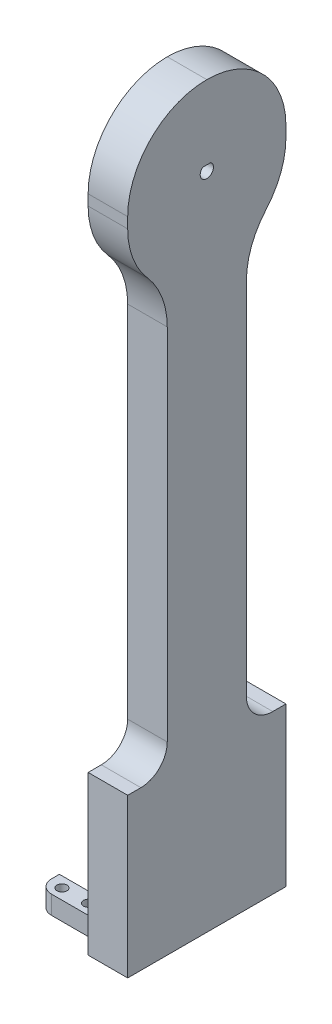
SolidWorks part; units mm, degrees
ref_plane "Front Plane" through (0, 0, 0) normal (0, 0, 1) x (1, 0, 0)
ref_plane "Top Plane" through (0, 0, 0) normal (0, 1, 0) x (1, 0, 0)
ref_plane "Right Plane" through (0, 0, 0) normal (1, 0, 0) x (0, 0, -1)
sketch "Sketch1" plane through (0, 0, 0) normal (1, 0, 0) x (0, 0, -1)
  line L1 (30, -30) -> (-30, -30)
  line L2 (30, -30) -> (30, 30)
  line L3 (30, 30) -> (-30, 30)
  line L4 (-30, -30) -> (-30, 30)
  line L5 (30, -30) -> (-30, 30) construction
  line L6 (30, 30) -> (-30, -30) construction
  point P0 (0, 0)
  dimension "D1" = 60
  dimension "D2" = 60
extrude "Boss-Extrude1" add sketch "Sketch1" along normal blind 15
sketch "Sketch2" plane through (15, 0, 0) normal (1, 0, 0) x (0, 0, -1)
  line L0 (0, 0) -> (0, 30) construction
  line L1 (30, 30) -> (-30, 30) construction
  line L2 (1.5, 2) -> (-1.5, 2)
  circle A0 centre (0, 0) radius 2.5
  dimension "D1" = 5
  dimension "D2" = 3
extrude "Cut-Extrude1" cut sketch "Sketch2" against normal up to surface (15 mm away) contours A0 region at (15, -0.1209, 0) up to face at (0, 0, 0)
sketch "Sketch8" plane through (0, -30, 0) normal (0, -1, 0) x (1, 0, 0)
  line L0 (0, 30) -> (0, 15) construction
  line L1 (0, 30) -> (0, -30) construction
  line L2 (15, 30) -> (15, -30) construction
  line L3 (0, 15) -> (15, 15)
  line L4 (0, 15) -> (0, -15)
  line L5 (0, -15) -> (15, -15)
  line L6 (15, 15) -> (15, -15)
  line L7 (0, -15) -> (0, -30) construction
  dimension "D1" = 30
extrude "Boss-Extrude2" add sketch "Sketch8" along normal blind 160
sketch "Sketch9" plane through (0, -190, 0) normal (0, -1, 0) x (1, 0, 0)
  line L0 (0, 0) -> (0, 30)
  line L1 (0, 15) -> (0, -15) construction
  line L2 (15, 30) -> (15, -30)
  line L3 (15, -30) -> (0, -30)
  line L4 (15, 30) -> (0, 30)
  line L5 (0, -30) -> (0, 0)
  dimension "D1" = 60
extrude "Boss-Extrude3" add sketch "Sketch9" along normal blind 60
sketch "Sketch10" plane through (0, 0, 0) normal (-1, 0, 0) x (0, 0, 1)
  line L0 (30, -250) -> (30, -245) construction
  line L1 (30, -250) -> (30, -190) construction
  line L2 (30, -245) -> (28.89, -245) construction
  line L3 (0, -250) -> (0, -194.4433) construction
  line L4 (28.89, -245) -> (20.89, -245)
  line L5 (28.89, -245) -> (28.89, -238)
  line L6 (28.89, -238) -> (20.89, -238)
  line L7 (20.89, -245) -> (20.89, -238)
  line L8 (30, -250) -> (-30, -250) construction
  line L9 (-20.89, -245) -> (-20.89, -238)
  line L10 (-28.89, -238) -> (-20.89, -238)
  line L11 (-28.89, -245) -> (-28.89, -238)
  line L12 (-28.89, -245) -> (-20.89, -245)
  line L13 (24.89, -245) -> (-24.89, -245) construction
  dimension "D1" = 5
  dimension "D2" = 7
  dimension "D3" = 8
  dimension "D4" = 49.78
extrude "Boss-Extrude4" add sketch "Sketch10" along normal blind 20
sketch "Sketch12" plane through (0, -245, 0) normal (0, -1, 0) x (1, 0, 0)
  line L0 (-20, 28.89) -> (-20, 24.89) construction
  line L1 (-20, 20.89) -> (-20, 28.89) construction
  line L2 (-20, 24.89) -> (-15.025, 24.89) construction
  line L3 (-15.025, 24.89) -> (-4.975, 24.89) construction
  line L4 (-4.975, 24.89) -> (0, 24.89) construction
  line L5 (0, 20.89) -> (0, 28.89) construction
  line L6 (0, 24.89) -> (0, -24.89) construction
  line L7 (0, -28.89) -> (0, -20.89) construction
  line L8 (0, 0) -> (-23.535, 0) construction
  circle A0 centre (-15.025, 24.89) radius 1.9
  circle A1 centre (-4.975, 24.89) radius 1.9
  circle A2 centre (-4.975, -24.89) radius 1.9
  circle A3 centre (-15.025, -24.89) radius 1.9
  dimension "D2" = 3.8
  dimension "D1" = 10.05
extrude "Cut-Extrude2" cut sketch "Sketch12" against normal up to surface (7 mm away) up to face at (-10, -238, 24.89)
fillet "Fillet1" radius 30 4 edges at (7.5, -30, -30) (7.5, 30, -30) (7.5, -30, 30) (7.5, 30, 30)
fillet "Fillet2" radius 30 2 edges at (7.5, -30, -15) (7.5, -30, 15)
fillet "Fillet4" radius 10 2 edges at (7.5, -190, -15) (7.5, -190, 15)
fillet "Fillet5" radius 5 2 edges at (-20, -241.5, 28.89) (-20, -241.5, -28.89)
